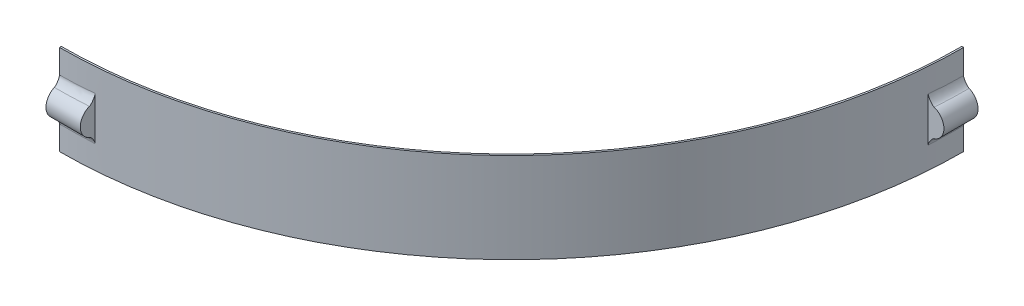
SolidWorks part; units mm, degrees
ref_plane "Front Plane" through (0, 0, 0) normal (0, 0, 1) x (1, 0, 0)
ref_plane "Top Plane" through (0, 0, 0) normal (0, 1, 0) x (1, 0, 0)
ref_plane "Right Plane" through (0, 0, 0) normal (1, 0, 0) x (0, 0, -1)
sketch "Sketch1" plane through (0, 0, 0) normal (0, 0, 1) x (1, 0, 0)
  line L0 (0, 3.3639) -> (0, -36.2756) construction
  line L1 (127.254, 12.7) -> (126.746, 12.7)
  line L2 (127.254, 12.7) -> (127.254, -12.7)
  line L3 (127.254, -12.7) -> (126.746, -12.7)
  line L4 (126.746, 12.7) -> (126.746, -12.7)
  line L5 (127.254, 12.7) -> (126.746, -12.7) construction
  line L6 (127.254, -12.7) -> (126.746, 12.7) construction
  point P0 (127, 0)
  dimension "D1" = 25.4
  dimension "D2" = 0.508
  dimension "D3" = 127
revolve "Revolve1" add sketch "Sketch1" angle 90 about L0
sketch "Sketch4" plane through (0, 0, 0) normal (-1, 0, 0) x (0, 0, 1)
  line L0 (126.746, 12.7) -> (126.746, -12.7) construction
  circle A0 centre (127, 0) radius 4.064
  point P2 (126.746, 0)
  dimension "D2" = 8.128
  dimension "D1" = 0.254
extrude "Boss-Extrude1" add sketch "Sketch4" against normal blind 9.652
sketch "Sketch6" plane through (9.652, 0, 0) normal (1, 0, 0) x (0, 0, -1)
  circle A0 centre (-127, 0) radius 3.175
  circle A2 centre (-127, 0) radius 4.064 construction
  dimension "D1" = 6.35
fillet "Fillet6" radius 2.54 2 edges at (8.128, 4.064, 126.9942) (1.5277, -4.0566, 127.2448) conic radius 5.08
fillet "Fillet8" radius 2.54 2 edges at (8.128, -4.0313, 126.4851) (1.5276, 4.0555, 126.7368) conic radius 5.08
sketch "Sketch7" plane through (0, 0, 0) normal (0, 0, -1) x (-1, 0, 0)
  line L0 (-127.254, -12.7) -> (-127.254, 12.7) construction
  circle A0 centre (-127.254, -0.254) radius 4.064
  point P2 (-127.254, 0)
  dimension "D1" = 8.128
  dimension "D2" = 0.254
extrude "Boss-Extrude2" add sketch "Sketch7" against normal blind 9.6012
sketch "Sketch8" plane through (0, 0, 9.6012) normal (0, 0, 1) x (1, 0, 0)
  circle A0 centre (127.254, -0.254) radius 3.175
  circle A1 centre (127.254, -0.254) radius 4.064 construction
  dimension "D1" = 6.35
fillet "Fillet11" radius 2.54 4 edges at (126.7374, -4.285, 1.4767) (126.4851, 3.7366, 8.128) (126.9942, -4.3097, 8.128) (127.2454, 3.81, 1.4767) conic radius 5.08
sketch "Sketch9" plane through (0, 0, 0) normal (-1, 0, 0) x (0, 0, 1)
  circle A0 centre (127, 0) radius 3.175
  dimension "D1" = 6.35
extrude "Cut-Extrude1" cut sketch "Sketch9" against normal blind 9.525
sketch "Sketch10" plane through (0, 0, 0) normal (0, 0, -1) x (-1, 0, 0)
  circle A0 centre (-127.254, -0.254) radius 3.175
extrude "Cut-Extrude2" cut sketch "Sketch10" against normal blind 9.525
